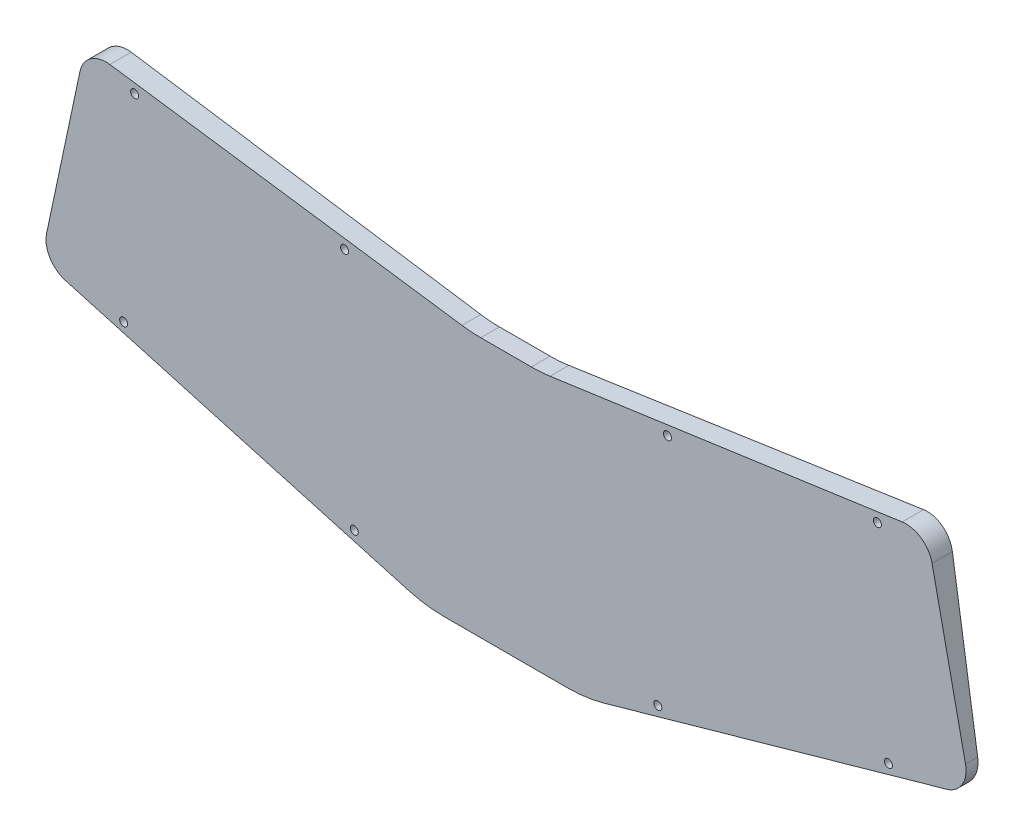
SolidWorks part; units mm, degrees
ref_plane "Front Plane" through (0, 0, 0) normal (0, 0, 1) x (1, 0, 0)
ref_plane "Top Plane" through (0, 0, 0) normal (0, 1, 0) x (1, 0, 0)
ref_plane "Right Plane" through (0, 0, 0) normal (1, 0, 0) x (0, 0, -1)
sketch "Model" plane through (0, 0, 0) normal (0, 0, 1) x (1, 0, 0)
  line L0 (325.3126, 39.9244) -> (319.5653, 66.9637)
  line L1 (325.3126, 39.9244) -> (332.0603, 8.179)
  line L2 (322.3782, 39.3007) -> (316.6308, 66.34)
  line L3 (322.3782, 39.3007) -> (329.1259, 7.5553)
  line L4 (306.4458, 71.4818) -> (308.8024, 71.8155)
  line L5 (13.8071, 71.4818) -> (11.4504, 71.8155)
  line L6 (-5.0598, 39.9244) -> (-11.8075, 8.179)
  line L7 (-2.1254, 39.3007) -> (-8.8731, 7.5553)
  line L8 (-5.0598, 39.9244) -> (0.6876, 66.9637)
  line L9 (-2.1254, 39.3007) -> (3.622, 66.34)
  line L10 (26.3327, -9.1816) -> (48.3039, -15.3856)
  line L11 (48.3039, -15.3856) -> (93.7705, -28.2242)
  line L12 (-3.9283, -0.6367) -> (7.4742, -3.8564)
  line L13 (90.0873, 60.6806) -> (30.9176, 69.0589)
  line L14 (210.7632, 57.9332) -> (177.0346, 53.1572)
  line L15 (169.604, 52.6338) -> (150.6488, 52.6338)
  line L16 (143.2182, 53.1572) -> (109.4896, 57.9332)
  line L17 (289.3352, 69.0589) -> (230.1656, 60.6806)
  line L18 (312.7787, -3.8564) -> (324.1811, -0.6367)
  line L19 (226.4824, -28.2242) -> (271.949, -15.3856)
  line L20 (271.949, -15.3856) -> (293.9202, -9.1816)
  line L21 (112.629, -33.5493) -> (124.2783, -36.8388)
  line L22 (137.0504, -38.6074) -> (160.1264, -38.6074)
  line L23 (160.1264, -38.6074) -> (183.2025, -38.6074)
  line L24 (195.9746, -36.8388) -> (207.6239, -33.5493)
  line L25 (169.604, 55.6338) -> (150.6488, 55.6338)
  line L26 (308.3818, 74.7858) -> (176.614, 56.1276)
  line L27 (272.7642, -18.2727) -> (324.9963, -3.5238)
  line L28 (196.7898, -39.7259) -> (272.7642, -18.2727)
  line L29 (160.1264, -41.6074) -> (183.2025, -41.6074)
  line L30 (137.0504, -41.6074) -> (160.1264, -41.6074)
  line L31 (47.4886, -18.2727) -> (123.463, -39.7259)
  line L32 (-4.7435, -3.5238) -> (47.4886, -18.2727)
  line L33 (143.6388, 56.1276) -> (11.8711, 74.7858)
  line L34 (196.5845, -32.4293) -> (202.5988, -29.3648)
  line L35 (190.1194, -20.2914) -> (196.2483, -32.32)
  line L36 (202.2573, -13.8263) -> (190.2287, -19.9552)
  line L37 (208.7224, -25.9641) -> (202.5935, -13.9355)
  line L38 (202.5988, -29.3648) -> (208.6131, -26.3004)
  line L39 (234.2278, -18.5408) -> (231.421, -5.3358)
  line L40 (220.8303, -21.6441) -> (234.0353, -18.8373)
  line L41 (217.7269, -8.2465) -> (220.5338, -21.4515)
  line L42 (231.1245, -5.1432) -> (217.9195, -7.95)
  line L43 (253.2284, -16.5467) -> (250.4216, -3.3417)
  line L44 (239.8309, -19.6501) -> (253.0359, -16.8433)
  line L45 (236.7276, -6.2525) -> (239.5344, -19.4575)
  line L46 (250.1251, -3.1492) -> (236.9201, -5.956)
  line L47 (210.4452, 1.9626) -> (207.6384, 15.1676)
  line L48 (197.0477, -1.1407) -> (210.2527, 1.6661)
  line L49 (193.9443, 12.2568) -> (196.7512, -0.9482)
  line L50 (207.3419, 15.3602) -> (194.1369, 12.5533)
  line L51 (206.4949, 20.5474) -> (203.6881, 33.7524)
  line L52 (193.0973, 17.4441) -> (206.3023, 20.2509)
  line L53 (189.994, 30.8416) -> (192.8008, 17.6366)
  line L54 (203.3916, 33.945) -> (190.1866, 31.1382)
  line L55 (202.5446, 39.1322) -> (199.7378, 52.3372)
  line L56 (189.147, 36.0289) -> (202.352, 38.8357)
  line L57 (186.0437, 49.4264) -> (188.8505, 36.2214)
  line L58 (199.4413, 52.5298) -> (186.2363, 49.723)
  line L59 (230.2775, 0.044) -> (227.4707, 13.249)
  line L60 (216.8799, -3.0593) -> (230.0849, -0.2525)
  line L61 (213.7766, 10.3383) -> (216.5834, -2.8667)
  line L62 (227.1742, 13.4416) -> (213.9692, 10.6348)
  line L63 (226.3272, 18.6288) -> (223.5204, 31.8338)
  line L64 (212.9296, 15.5255) -> (226.1346, 18.3323)
  line L65 (209.8263, 28.9231) -> (212.6331, 15.7181)
  line L66 (223.2239, 32.0264) -> (210.0189, 29.2196)
  line L67 (222.3769, 37.2136) -> (219.57, 50.4186)
  line L68 (208.9793, 34.1103) -> (222.1843, 36.9171)
  line L69 (205.876, 47.5079) -> (208.6828, 34.3029)
  line L70 (219.2735, 50.6112) -> (206.0685, 47.8044)
  line L71 (249.2781, 2.0381) -> (246.4713, 15.2431)
  line L72 (235.8806, -1.0653) -> (249.0856, 1.7416)
  line L73 (232.7772, 12.3323) -> (235.5841, -0.8727)
  line L74 (246.1748, 15.4356) -> (232.9698, 12.6288)
  line L75 (245.3278, 20.6229) -> (242.521, 33.8279)
  line L76 (231.9302, 17.5195) -> (245.1352, 20.3264)
  line L77 (228.8269, 30.9171) -> (231.6337, 17.7121)
  line L78 (242.2245, 34.0204) -> (229.0195, 31.2136)
  line L79 (241.3775, 39.2077) -> (238.5707, 52.4127)
  line L80 (227.9799, 36.1044) -> (241.1849, 38.9112)
  line L81 (224.8766, 49.5019) -> (227.6834, 36.2969)
  line L82 (238.2742, 52.6052) -> (225.0692, 49.7984)
  line L83 (271.2935, -10.151) -> (268.4867, 3.0539)
  line L84 (257.8959, -13.2544) -> (271.1009, -10.4476)
  line L85 (254.7926, 0.1432) -> (257.5994, -13.0618)
  line L86 (268.1901, 3.2465) -> (254.9852, 0.4397)
  line L87 (267.3431, 8.4338) -> (264.5363, 21.6387)
  line L88 (253.9456, 5.3304) -> (267.1506, 8.1372)
  line L89 (250.8423, 18.728) -> (253.6491, 5.523)
  line L90 (264.2398, 21.8313) -> (251.0348, 19.0245)
  line L91 (263.3928, 27.0186) -> (260.586, 40.2236)
  line L92 (249.9953, 23.9152) -> (263.2003, 26.722)
  line L93 (246.892, 37.3128) -> (249.6988, 24.1078)
  line L94 (260.2895, 40.4161) -> (247.0845, 37.6093)
  line L95 (259.4425, 45.6034) -> (256.6357, 58.8084)
  line L96 (246.045, 42.5) -> (259.2499, 45.3069)
  line L97 (242.9416, 55.8976) -> (245.7484, 42.6926)
  line L98 (256.3392, 59.0009) -> (243.1342, 56.1941)
  line L99 (286.4477, 9.9387) -> (283.6409, 23.1437)
  line L100 (273.0502, 6.8354) -> (286.2552, 9.6422)
  line L101 (269.9469, 20.2329) -> (272.7537, 7.0279)
  line L102 (283.3444, 23.3363) -> (270.1394, 20.5295)
  line L103 (282.4974, 28.5235) -> (279.6906, 41.7285)
  line L104 (269.0999, 25.4202) -> (282.3049, 28.227)
  line L105 (265.9965, 38.8177) -> (268.8033, 25.6128)
  line L106 (279.3941, 41.9211) -> (266.1891, 39.1143)
  line L107 (278.5471, 47.1083) -> (275.7403, 60.3133)
  line L108 (265.1495, 44.005) -> (278.3545, 46.8118)
  line L109 (262.0462, 57.4025) -> (264.853, 44.1976)
  line L110 (275.4438, 60.5059) -> (262.2388, 57.6991)
  line L111 (305.5523, 11.4437) -> (302.7455, 24.6487)
  line L112 (292.1548, 8.3403) -> (305.3598, 11.1471)
  line L113 (289.0514, 21.7379) -> (291.8582, 8.5329)
  line L114 (302.449, 24.8412) -> (289.244, 22.0344)
  line L115 (301.602, 30.0285) -> (298.7952, 43.2335)
  line L116 (288.2044, 26.9251) -> (301.4094, 29.732)
  line L117 (285.1011, 40.3227) -> (287.9079, 27.1177)
  line L118 (298.4987, 43.426) -> (285.2937, 40.6192)
  line L119 (297.6517, 48.6133) -> (294.8449, 61.8183)
  line L120 (284.2541, 45.5099) -> (297.4591, 48.3168)
  line L121 (281.1508, 58.9075) -> (283.9576, 45.7025)
  line L122 (294.5483, 62.0108) -> (281.3434, 59.204)
  line L123 (324.5529, 13.4377) -> (321.7461, 26.6427)
  line L124 (311.1554, 10.3344) -> (324.3604, 13.1412)
  line L125 (308.0521, 23.7319) -> (310.8589, 10.5269)
  line L126 (321.4496, 26.8352) -> (308.2446, 24.0284)
  line L127 (320.6026, 32.0225) -> (317.7958, 45.2275)
  line L128 (307.2051, 28.9192) -> (320.4101, 31.726)
  line L129 (304.1017, 42.3167) -> (306.9086, 29.1117)
  line L130 (317.4993, 45.42) -> (304.2943, 42.6132)
  line L131 (316.6523, 50.6073) -> (313.8455, 63.8123)
  line L132 (313.549, 64.0049) -> (300.344, 61.198)
  line L133 (300.1514, 60.9015) -> (302.9582, 47.6965)
  line L134 (303.2547, 47.504) -> (316.4597, 50.3108)
  line L135 (123.6683, -32.4293) -> (117.654, -29.3648)
  line L136 (130.1334, -20.2914) -> (124.0045, -32.32)
  line L137 (117.9956, -13.8263) -> (130.0242, -19.9552)
  line L138 (111.5305, -25.9641) -> (117.6593, -13.9355)
  line L139 (117.654, -29.3648) -> (111.6397, -26.3004)
  line L140 (86.025, -18.5408) -> (88.8318, -5.3358)
  line L141 (99.4226, -21.6441) -> (86.2176, -18.8373)
  line L142 (102.5259, -8.2465) -> (99.7191, -21.4515)
  line L143 (89.1283, -5.1432) -> (102.3333, -7.95)
  line L144 (67.0244, -16.5467) -> (69.8312, -3.3417)
  line L145 (80.4219, -19.6501) -> (67.2169, -16.8433)
  line L146 (83.5253, -6.2525) -> (80.7184, -19.4575)
  line L147 (70.1277, -3.1492) -> (83.3327, -5.956)
  line L148 (109.8076, 1.9626) -> (112.6144, 15.1676)
  line L149 (123.2052, -1.1407) -> (110.0002, 1.6661)
  line L150 (126.3085, 12.2568) -> (123.5017, -0.9482)
  line L151 (112.9109, 15.3602) -> (126.1159, 12.5533)
  line L152 (113.7579, 20.5474) -> (116.5647, 33.7524)
  line L153 (127.1555, 17.4441) -> (113.9505, 20.2509)
  line L154 (130.2588, 30.8416) -> (127.452, 17.6366)
  line L155 (116.8613, 33.945) -> (130.0662, 31.1382)
  line L156 (117.7083, 39.1322) -> (120.5151, 52.3372)
  line L157 (131.1058, 36.0289) -> (117.9008, 38.8357)
  line L158 (134.2091, 49.4264) -> (131.4023, 36.2214)
  line L159 (120.8116, 52.5298) -> (134.0166, 49.723)
  line L160 (89.9753, 0.044) -> (92.7821, 13.249)
  line L161 (103.3729, -3.0593) -> (90.1679, -0.2525)
  line L162 (106.4762, 10.3383) -> (103.6694, -2.8667)
  line L163 (93.0787, 13.4416) -> (106.2836, 10.6348)
  line L164 (93.9257, 18.6288) -> (96.7325, 31.8338)
  line L165 (107.3232, 15.5255) -> (94.1182, 18.3323)
  line L166 (110.4265, 28.9231) -> (107.6197, 15.7181)
  line L167 (97.029, 32.0264) -> (110.234, 29.2196)
  line L168 (97.876, 37.2136) -> (100.6828, 50.4186)
  line L169 (111.2735, 34.1103) -> (98.0685, 36.9171)
  line L170 (114.3769, 47.5079) -> (111.57, 34.3029)
  line L171 (100.9793, 50.6112) -> (114.1843, 47.8044)
  line L172 (70.9747, 2.0381) -> (73.7815, 15.2431)
  line L173 (84.3723, -1.0653) -> (71.1673, 1.7416)
  line L174 (87.4756, 12.3323) -> (84.6688, -0.8727)
  line L175 (74.078, 15.4356) -> (87.283, 12.6288)
  line L176 (74.925, 20.6229) -> (77.7318, 33.8279)
  line L177 (88.3226, 17.5195) -> (75.1176, 20.3264)
  line L178 (91.4259, 30.9171) -> (88.6191, 17.7121)
  line L179 (78.0284, 34.0204) -> (91.2333, 31.2136)
  line L180 (78.8753, 39.2077) -> (81.6822, 52.4127)
  line L181 (92.2729, 36.1044) -> (79.0679, 38.9112)
  line L182 (95.3762, 49.5019) -> (92.5694, 36.2969)
  line L183 (81.9787, 52.6052) -> (95.1837, 49.7984)
  line L184 (48.9594, -10.151) -> (51.7662, 3.0539)
  line L185 (62.3569, -13.2544) -> (49.1519, -10.4476)
  line L186 (65.4602, 0.1432) -> (62.6534, -13.0618)
  line L187 (52.0627, 3.2465) -> (65.2677, 0.4397)
  line L188 (52.9097, 8.4338) -> (55.7165, 21.6387)
  line L189 (66.3072, 5.3304) -> (53.1022, 8.1372)
  line L190 (69.4106, 18.728) -> (66.6037, 5.523)
  line L191 (56.013, 21.8313) -> (69.218, 19.0245)
  line L192 (56.86, 27.0186) -> (59.6668, 40.2236)
  line L193 (70.2576, 23.9152) -> (57.0526, 26.722)
  line L194 (73.3609, 37.3128) -> (70.5541, 24.1078)
  line L195 (59.9633, 40.4161) -> (73.1683, 37.6093)
  line L196 (60.8103, 45.6034) -> (63.6171, 58.8084)
  line L197 (74.2079, 42.5) -> (61.0029, 45.3069)
  line L198 (77.3112, 55.8976) -> (74.5044, 42.6926)
  line L199 (63.9136, 59.0009) -> (77.1186, 56.1941)
  line L200 (33.8051, 9.9387) -> (36.6119, 23.1437)
  line L201 (47.2026, 6.8354) -> (33.9977, 9.6422)
  line L202 (50.306, 20.2329) -> (47.4992, 7.0279)
  line L203 (36.9084, 23.3363) -> (50.1134, 20.5295)
  line L204 (37.7554, 28.5235) -> (40.5622, 41.7285)
  line L205 (51.153, 25.4202) -> (37.948, 28.227)
  line L206 (54.2563, 38.8177) -> (51.4495, 25.6128)
  line L207 (40.8587, 41.9211) -> (54.0637, 39.1143)
  line L208 (41.7057, 47.1083) -> (44.5125, 60.3133)
  line L209 (55.1033, 44.005) -> (41.8983, 46.8118)
  line L210 (58.2066, 57.4025) -> (55.3998, 44.1976)
  line L211 (44.8091, 60.5059) -> (58.0141, 57.6991)
  line L212 (14.7005, 11.4437) -> (17.5073, 24.6487)
  line L213 (28.0981, 8.3403) -> (14.8931, 11.1471)
  line L214 (31.2014, 21.7379) -> (28.3946, 8.5329)
  line L215 (17.8038, 24.8412) -> (31.0088, 22.0344)
  line L216 (18.6508, 30.0285) -> (21.4576, 43.2335)
  line L217 (32.0484, 26.9251) -> (18.8434, 29.732)
  line L218 (35.1517, 40.3227) -> (32.3449, 27.1177)
  line L219 (21.7542, 43.426) -> (34.9592, 40.6192)
  line L220 (22.6012, 48.6133) -> (25.408, 61.8183)
  line L221 (35.9987, 45.5099) -> (22.7937, 48.3168)
  line L222 (39.102, 58.9075) -> (36.2952, 45.7025)
  line L223 (25.7045, 62.0108) -> (38.9095, 59.204)
  line L224 (-4.3001, 13.4377) -> (-1.4933, 26.6427)
  line L225 (9.0974, 10.3344) -> (-4.1076, 13.1412)
  line L226 (12.2008, 23.7319) -> (9.394, 10.5269)
  line L227 (-1.1968, 26.8352) -> (12.0082, 24.0284)
  line L228 (-0.3498, 32.0225) -> (2.457, 45.2275)
  line L229 (13.0478, 28.9192) -> (-0.1572, 31.726)
  line L230 (16.1511, 42.3167) -> (13.3443, 29.1117)
  line L231 (2.7535, 45.42) -> (15.9585, 42.6132)
  line L232 (3.6005, 50.6073) -> (6.4073, 63.8123)
  line L233 (6.7039, 64.0049) -> (19.9088, 61.198)
  line L234 (20.1014, 60.9015) -> (17.2946, 47.6965)
  line L235 (16.9981, 47.504) -> (3.7931, 50.3108)
  circle A0 centre (21.1464, 69.9376) radius 1.5
  circle A1 centre (299.1065, 69.9376) radius 1.5
  arc A2 (296.6652, 67.2112) -> (289.3352, 69.0589) centre (290.7372, 59.1577) ccw
  arc A3 (306.4458, 71.4818) -> (302.641, 68.6986) centre (307.1468, 66.5312) ccw
  arc A4 (17.6118, 68.6986) -> (13.8071, 71.4818) centre (13.106, 66.5312) ccw
  arc A5 (30.9176, 69.0589) -> (23.5876, 67.2112) centre (29.5156, 59.1577) ccw
  arc A6 (17.6118, 68.6986) -> (23.5876, 67.2112) centre (21.2165, 70.4326) ccw
  arc A7 (296.6652, 67.2112) -> (302.641, 68.6986) centre (299.0364, 70.4326) ccw
  arc A8 (324.9963, -3.5238) -> (332.0603, 8.179) centre (322.2789, 6.0999) ccw
  arc A9 (319.5653, 66.9637) -> (308.3818, 74.7858) centre (309.7838, 64.8846) ccw
  arc A10 (324.1811, -0.6367) -> (329.1259, 7.5553) centre (322.2789, 6.0999) ccw
  arc A11 (316.6308, 66.34) -> (308.8024, 71.8155) centre (309.7838, 64.8846) ccw
  arc A12 (11.8711, 74.7858) -> (0.6876, 66.9637) centre (10.469, 64.8846) ccw
  arc A13 (-11.8075, 8.179) -> (-4.7435, -3.5238) centre (-2.026, 6.0999) ccw
  arc A14 (-8.8731, 7.5553) -> (-3.9283, -0.6367) centre (-2.026, 6.0999) ccw
  arc A15 (11.4504, 71.8155) -> (3.622, 66.34) centre (10.469, 64.8846) ccw
  circle A16 centre (303.2135, -6.0378) radius 1.5
  circle A17 centre (17.0393, -6.0378) radius 1.5
  arc A18 (293.9202, -9.1816) -> (299.8789, -4.5301) centre (291.2027, 0.4421) ccw
  arc A19 (305.2671, -3.0086) -> (312.7787, -3.8564) centre (310.0612, 5.7673) ccw
  arc A20 (20.3739, -4.5301) -> (26.3327, -9.1816) centre (29.0501, 0.4421) ccw
  arc A21 (7.4742, -3.8564) -> (14.9858, -3.0086) centre (10.1916, 5.7673) ccw
  arc A22 (20.3739, -4.5301) -> (14.9858, -3.0086) centre (16.9034, -6.519) ccw
  arc A23 (305.2671, -3.0086) -> (299.8789, -4.5301) centre (303.3494, -6.519) ccw
  circle A24 centre (220.5345, 58.8118) radius 1.5
  circle A25 centre (99.7183, 58.8118) radius 1.5
  arc A26 (230.1656, 60.6806) -> (223.6367, 56.8704) centre (231.5676, 50.7793) ccw
  arc A27 (218.0932, 56.0855) -> (210.7632, 57.9332) centre (212.1652, 48.032) ccw
  arc A28 (96.6161, 56.8704) -> (90.0873, 60.6806) centre (88.6852, 50.7793) ccw
  arc A29 (109.4896, 57.9332) -> (102.1596, 56.0855) centre (108.0876, 48.032) ccw
  arc A30 (218.0932, 56.0855) -> (223.6367, 56.8704) centre (220.4644, 59.3069) ccw
  arc A31 (96.6161, 56.8704) -> (102.1596, 56.0855) centre (99.7884, 59.3069) ccw
  circle A32 centre (216.9173, -30.4056) radius 1.5
  arc A33 (218.9708, -27.3764) -> (226.4824, -28.2242) centre (223.7649, -18.6005) ccw
  arc A34 (207.6239, -33.5493) -> (213.5826, -28.8979) centre (204.9064, -23.9256) ccw
  circle A35 centre (103.3356, -30.4056) radius 1.5
  arc A36 (106.6702, -28.8979) -> (112.629, -33.5493) centre (115.3464, -23.9256) ccw
  arc A37 (93.7705, -28.2242) -> (101.2821, -27.3764) centre (96.4879, -18.6005) ccw
  arc A38 (218.9708, -27.3764) -> (213.5826, -28.8979) centre (217.0531, -30.8868) ccw
  arc A39 (106.6702, -28.8979) -> (101.2821, -27.3764) centre (103.1997, -30.8868) ccw
  arc A40 (169.604, 55.6338) -> (176.614, 56.1276) centre (169.604, 105.6338) ccw
  arc A41 (183.2025, -41.6074) -> (196.7898, -39.7259) centre (183.2025, 8.3926) ccw
  arc A42 (123.463, -39.7259) -> (137.0504, -41.6074) centre (137.0504, 8.3926) ccw
  arc A43 (143.6388, 56.1276) -> (150.6488, 55.6338) centre (150.6488, 105.6338) ccw
  arc A44 (196.2483, -32.32) -> (196.5845, -32.4293) centre (196.471, -32.2065) ccw
  arc A45 (190.2287, -19.9552) -> (190.1194, -20.2914) centre (190.3422, -20.1779) ccw
  arc A46 (202.5935, -13.9355) -> (202.2573, -13.8263) centre (202.3708, -14.049) ccw
  arc A47 (208.6131, -26.3004) -> (208.7224, -25.9641) centre (208.4996, -26.0776) ccw
  arc A48 (231.421, -5.3358) -> (231.1245, -5.1432) centre (231.1765, -5.3878) ccw
  arc A49 (217.9195, -7.95) -> (217.7269, -8.2465) centre (217.9715, -8.1946) ccw
  arc A50 (220.5338, -21.4515) -> (220.8303, -21.6441) centre (220.7783, -21.3996) ccw
  arc A51 (234.0353, -18.8373) -> (234.2278, -18.5408) centre (233.9833, -18.5927) ccw
  arc A52 (250.4216, -3.3417) -> (250.1251, -3.1492) centre (250.1771, -3.3937) ccw
  arc A53 (236.9201, -5.956) -> (236.7276, -6.2525) centre (236.9721, -6.2005) ccw
  arc A54 (239.5344, -19.4575) -> (239.8309, -19.6501) centre (239.7789, -19.4055) ccw
  arc A55 (253.0359, -16.8433) -> (253.2284, -16.5467) centre (252.9839, -16.5987) ccw
  arc A56 (207.6384, 15.1676) -> (207.3419, 15.3602) centre (207.3939, 15.1156) ccw
  arc A57 (194.1369, 12.5533) -> (193.9443, 12.2568) centre (194.1889, 12.3088) ccw
  arc A58 (196.7512, -0.9482) -> (197.0477, -1.1407) centre (196.9957, -0.8962) ccw
  arc A59 (210.2527, 1.6661) -> (210.4452, 1.9626) centre (210.2007, 1.9106) ccw
  arc A60 (203.6881, 33.7524) -> (203.3916, 33.945) centre (203.4436, 33.7004) ccw
  arc A61 (190.1866, 31.1382) -> (189.994, 30.8416) centre (190.2386, 30.8936) ccw
  arc A62 (192.8008, 17.6366) -> (193.0973, 17.4441) centre (193.0454, 17.6886) ccw
  arc A63 (206.3023, 20.2509) -> (206.4949, 20.5474) centre (206.2504, 20.4954) ccw
  arc A64 (199.7378, 52.3372) -> (199.4413, 52.5298) centre (199.4932, 52.2852) ccw
  arc A65 (186.2363, 49.723) -> (186.0437, 49.4264) centre (186.2882, 49.4784) ccw
  arc A66 (188.8505, 36.2214) -> (189.147, 36.0289) centre (189.095, 36.2734) ccw
  arc A67 (202.352, 38.8357) -> (202.5446, 39.1322) centre (202.3, 39.0802) ccw
  arc A68 (227.4707, 13.249) -> (227.1742, 13.4416) centre (227.2262, 13.1971) ccw
  arc A69 (213.9692, 10.6348) -> (213.7766, 10.3383) centre (214.0212, 10.3902) ccw
  arc A70 (216.5834, -2.8667) -> (216.8799, -3.0593) centre (216.828, -2.8147) ccw
  arc A71 (230.0849, -0.2525) -> (230.2775, 0.044) centre (230.033, -0.0079) ccw
  arc A72 (223.5204, 31.8338) -> (223.2239, 32.0264) centre (223.2758, 31.7819) ccw
  arc A73 (210.0189, 29.2196) -> (209.8263, 28.9231) centre (210.0708, 28.9751) ccw
  arc A74 (212.6331, 15.7181) -> (212.9296, 15.5255) centre (212.8776, 15.7701) ccw
  arc A75 (226.1346, 18.3323) -> (226.3272, 18.6288) centre (226.0826, 18.5769) ccw
  arc A76 (219.57, 50.4186) -> (219.2735, 50.6112) centre (219.3255, 50.3667) ccw
  arc A77 (206.0685, 47.8044) -> (205.876, 47.5079) centre (206.1205, 47.5599) ccw
  arc A78 (208.6828, 34.3029) -> (208.9793, 34.1103) centre (208.9273, 34.3549) ccw
  arc A79 (222.1843, 36.9171) -> (222.3769, 37.2136) centre (222.1323, 37.1617) ccw
  arc A80 (246.4713, 15.2431) -> (246.1748, 15.4356) centre (246.2268, 15.1911) ccw
  arc A81 (249.0856, 1.7416) -> (249.2781, 2.0381) centre (249.0336, 1.9861) ccw
  arc A82 (232.9698, 12.6288) -> (232.7772, 12.3323) centre (233.0218, 12.3843) ccw
  arc A83 (235.5841, -0.8727) -> (235.8806, -1.0653) centre (235.8286, -0.8207) ccw
  arc A84 (242.521, 33.8279) -> (242.2245, 34.0204) centre (242.2765, 33.7759) ccw
  arc A85 (229.0195, 31.2136) -> (228.8269, 30.9171) centre (229.0715, 30.9691) ccw
  arc A86 (231.6337, 17.7121) -> (231.9302, 17.5195) centre (231.8783, 17.7641) ccw
  arc A87 (245.1352, 20.3264) -> (245.3278, 20.6229) centre (245.0833, 20.5709) ccw
  arc A88 (238.5707, 52.4127) -> (238.2742, 52.6052) centre (238.3261, 52.3607) ccw
  arc A89 (225.0692, 49.7984) -> (224.8766, 49.5019) centre (225.1211, 49.5539) ccw
  arc A90 (227.6834, 36.2969) -> (227.9799, 36.1044) centre (227.9279, 36.3489) ccw
  arc A91 (241.1849, 38.9112) -> (241.3775, 39.2077) centre (241.1329, 39.1557) ccw
  arc A92 (268.4867, 3.0539) -> (268.1901, 3.2465) centre (268.2421, 3.002) ccw
  arc A93 (254.9852, 0.4397) -> (254.7926, 0.1432) centre (255.0371, 0.1952) ccw
  arc A94 (257.5994, -13.0618) -> (257.8959, -13.2544) centre (257.8439, -13.0098) ccw
  arc A95 (271.1009, -10.4476) -> (271.2935, -10.151) centre (271.0489, -10.203) ccw
  arc A96 (264.5363, 21.6387) -> (264.2398, 21.8313) centre (264.2918, 21.5868) ccw
  arc A97 (251.0348, 19.0245) -> (250.8423, 18.728) centre (251.0868, 18.78) ccw
  arc A98 (253.6491, 5.523) -> (253.9456, 5.3304) centre (253.8936, 5.575) ccw
  arc A99 (267.1506, 8.1372) -> (267.3431, 8.4338) centre (267.0986, 8.3818) ccw
  arc A100 (260.586, 40.2236) -> (260.2895, 40.4161) centre (260.3415, 40.1716) ccw
  arc A101 (247.0845, 37.6093) -> (246.892, 37.3128) centre (247.1365, 37.3648) ccw
  arc A102 (249.6988, 24.1078) -> (249.9953, 23.9152) centre (249.9433, 24.1598) ccw
  arc A103 (263.2003, 26.722) -> (263.3928, 27.0186) centre (263.1483, 26.9666) ccw
  arc A104 (256.6357, 58.8084) -> (256.3392, 59.0009) centre (256.3912, 58.7564) ccw
  arc A105 (243.1342, 56.1941) -> (242.9416, 55.8976) centre (243.1862, 55.9496) ccw
  arc A106 (245.7484, 42.6926) -> (246.045, 42.5) centre (245.993, 42.7446) ccw
  arc A107 (259.2499, 45.3069) -> (259.4425, 45.6034) centre (259.198, 45.5514) ccw
  arc A108 (283.6409, 23.1437) -> (283.3444, 23.3363) centre (283.3964, 23.0917) ccw
  arc A109 (270.1394, 20.5295) -> (269.9469, 20.2329) centre (270.1914, 20.2849) ccw
  arc A110 (272.7537, 7.0279) -> (273.0502, 6.8354) centre (272.9982, 7.0799) ccw
  arc A111 (286.2552, 9.6422) -> (286.4477, 9.9387) centre (286.2032, 9.8867) ccw
  arc A112 (279.6906, 41.7285) -> (279.3941, 41.9211) centre (279.4461, 41.6765) ccw
  arc A113 (266.1891, 39.1143) -> (265.9965, 38.8177) centre (266.2411, 38.8697) ccw
  arc A114 (268.8033, 25.6128) -> (269.0999, 25.4202) centre (269.0479, 25.6647) ccw
  arc A115 (282.3049, 28.227) -> (282.4974, 28.5235) centre (282.2529, 28.4715) ccw
  arc A116 (275.7403, 60.3133) -> (275.4438, 60.5059) centre (275.4957, 60.2613) ccw
  arc A117 (262.2388, 57.6991) -> (262.0462, 57.4025) centre (262.2908, 57.4545) ccw
  arc A118 (264.853, 44.1976) -> (265.1495, 44.005) centre (265.0976, 44.2495) ccw
  arc A119 (278.3545, 46.8118) -> (278.5471, 47.1083) centre (278.3026, 47.0563) ccw
  arc A120 (302.7455, 24.6487) -> (302.449, 24.8412) centre (302.501, 24.5967) ccw
  arc A121 (305.3598, 11.1471) -> (305.5523, 11.4437) centre (305.3078, 11.3917) ccw
  arc A122 (289.244, 22.0344) -> (289.0514, 21.7379) centre (289.296, 21.7899) ccw
  arc A123 (291.8582, 8.5329) -> (292.1548, 8.3403) centre (292.1028, 8.5849) ccw
  arc A124 (298.7952, 43.2335) -> (298.4987, 43.426) centre (298.5506, 43.1815) ccw
  arc A125 (285.2937, 40.6192) -> (285.1011, 40.3227) centre (285.3457, 40.3747) ccw
  arc A126 (287.9079, 27.1177) -> (288.2044, 26.9251) centre (288.1525, 27.1697) ccw
  arc A127 (301.4094, 29.732) -> (301.602, 30.0285) centre (301.3575, 29.9765) ccw
  arc A128 (294.8449, 61.8183) -> (294.5483, 62.0108) centre (294.6003, 61.7663) ccw
  arc A129 (281.3434, 59.204) -> (281.1508, 58.9075) centre (281.3953, 58.9595) ccw
  arc A130 (283.9576, 45.7025) -> (284.2541, 45.5099) centre (284.2021, 45.7545) ccw
  arc A131 (297.4591, 48.3168) -> (297.6517, 48.6133) centre (297.4071, 48.5613) ccw
  arc A132 (321.7461, 26.6427) -> (321.4496, 26.8352) centre (321.5016, 26.5907) ccw
  arc A133 (308.2446, 24.0284) -> (308.0521, 23.7319) centre (308.2966, 23.7839) ccw
  arc A134 (310.8589, 10.5269) -> (311.1554, 10.3344) centre (311.1034, 10.5789) ccw
  arc A135 (324.3604, 13.1412) -> (324.5529, 13.4377) centre (324.3084, 13.3857) ccw
  arc A136 (317.7958, 45.2275) -> (317.4993, 45.42) centre (317.5513, 45.1755) ccw
  arc A137 (306.9086, 29.1117) -> (307.2051, 28.9192) centre (307.1531, 29.1637) ccw
  arc A138 (320.4101, 31.726) -> (320.6026, 32.0225) centre (320.3581, 31.9705) ccw
  arc A139 (304.2943, 42.6132) -> (304.1017, 42.3167) centre (304.3463, 42.3687) ccw
  arc A140 (313.8455, 63.8123) -> (313.549, 64.0049) centre (313.601, 63.7603) ccw
  arc A141 (300.344, 61.198) -> (300.1514, 60.9015) centre (300.396, 60.9535) ccw
  arc A142 (316.4597, 50.3108) -> (316.6523, 50.6073) centre (316.4078, 50.5553) ccw
  arc A143 (302.9582, 47.6965) -> (303.2547, 47.504) centre (303.2028, 47.7485) ccw
  arc A144 (123.6683, -32.4293) -> (124.0045, -32.32) centre (123.7818, -32.2065) ccw
  arc A145 (130.1334, -20.2914) -> (130.0242, -19.9552) centre (129.9107, -20.1779) ccw
  arc A146 (117.9956, -13.8263) -> (117.6593, -13.9355) centre (117.8821, -14.049) ccw
  arc A147 (111.5305, -25.9641) -> (111.6397, -26.3004) centre (111.7532, -26.0776) ccw
  arc A148 (89.1283, -5.1432) -> (88.8318, -5.3358) centre (89.0764, -5.3878) ccw
  arc A149 (102.5259, -8.2465) -> (102.3333, -7.95) centre (102.2813, -8.1946) ccw
  arc A150 (99.4226, -21.6441) -> (99.7191, -21.4515) centre (99.4745, -21.3996) ccw
  arc A151 (86.025, -18.5408) -> (86.2176, -18.8373) centre (86.2695, -18.5927) ccw
  arc A152 (70.1277, -3.1492) -> (69.8312, -3.3417) centre (70.0757, -3.3937) ccw
  arc A153 (83.5253, -6.2525) -> (83.3327, -5.956) centre (83.2807, -6.2005) ccw
  arc A154 (80.4219, -19.6501) -> (80.7184, -19.4575) centre (80.4739, -19.4055) ccw
  arc A155 (67.0244, -16.5467) -> (67.2169, -16.8433) centre (67.2689, -16.5987) ccw
  arc A156 (112.9109, 15.3602) -> (112.6144, 15.1676) centre (112.859, 15.1156) ccw
  arc A157 (126.3085, 12.2568) -> (126.1159, 12.5533) centre (126.0639, 12.3088) ccw
  arc A158 (123.2052, -1.1407) -> (123.5017, -0.9482) centre (123.2571, -0.8962) ccw
  arc A159 (109.8076, 1.9626) -> (110.0002, 1.6661) centre (110.0521, 1.9106) ccw
  arc A160 (116.8613, 33.945) -> (116.5647, 33.7524) centre (116.8093, 33.7004) ccw
  arc A161 (130.2588, 30.8416) -> (130.0662, 31.1382) centre (130.0143, 30.8936) ccw
  arc A162 (127.1555, 17.4441) -> (127.452, 17.6366) centre (127.2075, 17.6886) ccw
  arc A163 (113.7579, 20.5474) -> (113.9505, 20.2509) centre (114.0025, 20.4954) ccw
  arc A164 (120.8116, 52.5298) -> (120.5151, 52.3372) centre (120.7596, 52.2852) ccw
  arc A165 (134.2091, 49.4264) -> (134.0166, 49.723) centre (133.9646, 49.4784) ccw
  arc A166 (131.1058, 36.0289) -> (131.4023, 36.2214) centre (131.1578, 36.2734) ccw
  arc A167 (117.7083, 39.1322) -> (117.9008, 38.8357) centre (117.9528, 39.0802) ccw
  arc A168 (93.0787, 13.4416) -> (92.7821, 13.249) centre (93.0267, 13.1971) ccw
  arc A169 (106.4762, 10.3383) -> (106.2836, 10.6348) centre (106.2317, 10.3902) ccw
  arc A170 (103.3729, -3.0593) -> (103.6694, -2.8667) centre (103.4249, -2.8147) ccw
  arc A171 (89.9753, 0.044) -> (90.1679, -0.2525) centre (90.2199, -0.0079) ccw
  arc A172 (97.029, 32.0264) -> (96.7325, 31.8338) centre (96.977, 31.7819) ccw
  arc A173 (110.4265, 28.9231) -> (110.234, 29.2196) centre (110.182, 28.9751) ccw
  arc A174 (107.3232, 15.5255) -> (107.6197, 15.7181) centre (107.3752, 15.7701) ccw
  arc A175 (93.9257, 18.6288) -> (94.1182, 18.3323) centre (94.1702, 18.5769) ccw
  arc A176 (100.9793, 50.6112) -> (100.6828, 50.4186) centre (100.9273, 50.3667) ccw
  arc A177 (114.3769, 47.5079) -> (114.1843, 47.8044) centre (114.1323, 47.5599) ccw
  arc A178 (111.2735, 34.1103) -> (111.57, 34.3029) centre (111.3255, 34.3549) ccw
  arc A179 (97.876, 37.2136) -> (98.0685, 36.9171) centre (98.1205, 37.1617) ccw
  arc A180 (74.078, 15.4356) -> (73.7815, 15.2431) centre (74.026, 15.1911) ccw
  arc A181 (70.9747, 2.0381) -> (71.1673, 1.7416) centre (71.2192, 1.9861) ccw
  arc A182 (87.4756, 12.3323) -> (87.283, 12.6288) centre (87.231, 12.3843) ccw
  arc A183 (84.3723, -1.0653) -> (84.6688, -0.8727) centre (84.4242, -0.8207) ccw
  arc A184 (78.0284, 34.0204) -> (77.7318, 33.8279) centre (77.9764, 33.7759) ccw
  arc A185 (91.4259, 30.9171) -> (91.2333, 31.2136) centre (91.1814, 30.9691) ccw
  arc A186 (88.3226, 17.5195) -> (88.6191, 17.7121) centre (88.3746, 17.7641) ccw
  arc A187 (74.925, 20.6229) -> (75.1176, 20.3264) centre (75.1696, 20.5709) ccw
  arc A188 (81.9787, 52.6052) -> (81.6822, 52.4127) centre (81.9267, 52.3607) ccw
  arc A189 (95.3762, 49.5019) -> (95.1837, 49.7984) centre (95.1317, 49.5539) ccw
  arc A190 (92.2729, 36.1044) -> (92.5694, 36.2969) centre (92.3249, 36.3489) ccw
  arc A191 (78.8753, 39.2077) -> (79.0679, 38.9112) centre (79.1199, 39.1557) ccw
  arc A192 (52.0627, 3.2465) -> (51.7662, 3.0539) centre (52.0107, 3.002) ccw
  arc A193 (65.4602, 0.1432) -> (65.2677, 0.4397) centre (65.2157, 0.1952) ccw
  arc A194 (62.3569, -13.2544) -> (62.6534, -13.0618) centre (62.4089, -13.0098) ccw
  arc A195 (48.9594, -10.151) -> (49.1519, -10.4476) centre (49.2039, -10.203) ccw
  arc A196 (56.013, 21.8313) -> (55.7165, 21.6387) centre (55.961, 21.5868) ccw
  arc A197 (69.4106, 18.728) -> (69.218, 19.0245) centre (69.166, 18.78) ccw
  arc A198 (66.3072, 5.3304) -> (66.6037, 5.523) centre (66.3592, 5.575) ccw
  arc A199 (52.9097, 8.4338) -> (53.1022, 8.1372) centre (53.1542, 8.3818) ccw
  arc A200 (59.9633, 40.4161) -> (59.6668, 40.2236) centre (59.9113, 40.1716) ccw
  arc A201 (73.3609, 37.3128) -> (73.1683, 37.6093) centre (73.1163, 37.3648) ccw
  arc A202 (70.2576, 23.9152) -> (70.5541, 24.1078) centre (70.3095, 24.1598) ccw
  arc A203 (56.86, 27.0186) -> (57.0526, 26.722) centre (57.1045, 26.9666) ccw
  arc A204 (63.9136, 59.0009) -> (63.6171, 58.8084) centre (63.8617, 58.7564) ccw
  arc A205 (77.3112, 55.8976) -> (77.1186, 56.1941) centre (77.0667, 55.9496) ccw
  arc A206 (74.2079, 42.5) -> (74.5044, 42.6926) centre (74.2599, 42.7446) ccw
  arc A207 (60.8103, 45.6034) -> (61.0029, 45.3069) centre (61.0549, 45.5514) ccw
  arc A208 (36.9084, 23.3363) -> (36.6119, 23.1437) centre (36.8564, 23.0917) ccw
  arc A209 (50.306, 20.2329) -> (50.1134, 20.5295) centre (50.0614, 20.2849) ccw
  arc A210 (47.2026, 6.8354) -> (47.4992, 7.0279) centre (47.2546, 7.0799) ccw
  arc A211 (33.8051, 9.9387) -> (33.9977, 9.6422) centre (34.0496, 9.8867) ccw
  arc A212 (40.8587, 41.9211) -> (40.5622, 41.7285) centre (40.8068, 41.6765) ccw
  arc A213 (54.2563, 38.8177) -> (54.0637, 39.1143) centre (54.0118, 38.8697) ccw
  arc A214 (51.153, 25.4202) -> (51.4495, 25.6128) centre (51.2049, 25.6647) ccw
  arc A215 (37.7554, 28.5235) -> (37.948, 28.227) centre (38, 28.4715) ccw
  arc A216 (44.8091, 60.5059) -> (44.5125, 60.3133) centre (44.7571, 60.2613) ccw
  arc A217 (58.2066, 57.4025) -> (58.0141, 57.6991) centre (57.9621, 57.4545) ccw
  arc A218 (55.1033, 44.005) -> (55.3998, 44.1976) centre (55.1553, 44.2495) ccw
  arc A219 (41.7057, 47.1083) -> (41.8983, 46.8118) centre (41.9503, 47.0563) ccw
  arc A220 (17.8038, 24.8412) -> (17.5073, 24.6487) centre (17.7519, 24.5967) ccw
  arc A221 (14.7005, 11.4437) -> (14.8931, 11.1471) centre (14.945, 11.3917) ccw
  arc A222 (31.2014, 21.7379) -> (31.0088, 22.0344) centre (30.9569, 21.7899) ccw
  arc A223 (28.0981, 8.3403) -> (28.3946, 8.5329) centre (28.15, 8.5849) ccw
  arc A224 (21.7542, 43.426) -> (21.4576, 43.2335) centre (21.7022, 43.1815) ccw
  arc A225 (35.1517, 40.3227) -> (34.9592, 40.6192) centre (34.9072, 40.3747) ccw
  arc A226 (32.0484, 26.9251) -> (32.3449, 27.1177) centre (32.1004, 27.1697) ccw
  arc A227 (18.6508, 30.0285) -> (18.8434, 29.732) centre (18.8954, 29.9765) ccw
  arc A228 (25.7045, 62.0108) -> (25.408, 61.8183) centre (25.6525, 61.7663) ccw
  arc A229 (39.102, 58.9075) -> (38.9095, 59.204) centre (38.8575, 58.9595) ccw
  arc A230 (35.9987, 45.5099) -> (36.2952, 45.7025) centre (36.0507, 45.7545) ccw
  arc A231 (22.6012, 48.6133) -> (22.7937, 48.3168) centre (22.8457, 48.5613) ccw
  arc A232 (-1.1968, 26.8352) -> (-1.4933, 26.6427) centre (-1.2488, 26.5907) ccw
  arc A233 (12.2008, 23.7319) -> (12.0082, 24.0284) centre (11.9562, 23.7839) ccw
  arc A234 (9.0974, 10.3344) -> (9.394, 10.5269) centre (9.1494, 10.5789) ccw
  arc A235 (-4.3001, 13.4377) -> (-4.1076, 13.1412) centre (-4.0556, 13.3857) ccw
  arc A236 (2.7535, 45.42) -> (2.457, 45.2275) centre (2.7016, 45.1755) ccw
  arc A237 (13.0478, 28.9192) -> (13.3443, 29.1117) centre (13.0997, 29.1637) ccw
  arc A238 (-0.3498, 32.0225) -> (-0.1572, 31.726) centre (-0.1053, 31.9705) ccw
  arc A239 (16.1511, 42.3167) -> (15.9585, 42.6132) centre (15.9065, 42.3687) ccw
  arc A240 (6.7039, 64.0049) -> (6.4073, 63.8123) centre (6.6519, 63.7603) ccw
  arc A241 (20.1014, 60.9015) -> (19.9088, 61.198) centre (19.8569, 60.9535) ccw
  arc A242 (3.6005, 50.6073) -> (3.7931, 50.3108) centre (3.8451, 50.5553) ccw
  arc A243 (16.9981, 47.504) -> (17.2946, 47.6965) centre (17.0501, 47.7485) ccw
  arc A244 (169.604, 52.6338) -> (177.0346, 53.1572) centre (169.604, 105.6338) ccw
  arc A245 (143.2182, 53.1572) -> (150.6488, 52.6338) centre (150.6488, 105.6338) ccw
  arc A246 (124.2783, -36.8388) -> (137.0504, -38.6074) centre (137.0504, 8.3926) ccw
  arc A247 (183.2025, -38.6074) -> (195.9746, -36.8388) centre (183.2025, 8.3926) ccw
extrude "Boss-Extrude1" add sketch "Model" along normal blind 8 contours L23 A247 L24 A34 A38 A33 L19 L20 A18 A23 A19 L18 A10 L3 L2 A11 L4 A3 A7 A2 L17 A26 A30 A27 L14 A244 L15 A245 L16 A29 A31 A28 L13 A5 A6 A4 L5 A15 L9 L7 A14 L12 A21 A22 A20 L10 L11 A37 A39 A36 L21 | A43 L33 A12 L8 L6 A13 L32 L31 A42 L30 L29 A41 L28 L27 A8 L1 L0 A9 L26 A40 L25 A247 L23 L22 A246 L21 A36 A39 A37 L11 L10 A20 A22 A21 L12 A14 L7 L9 A15 L5 A4 A6 A5 L13 A28 A31 A29 L16 A245 L15 | L235 A243 L234 A241 L233 A240 L232 A242 | L220 A231 L221 A230 L222 A229 L223 A228 | L216 A227 L217 A226 L218 A225 L219 A224 | L230 A239 L231 A236 L228 A238 L229 A237 | L224 A235 L225 A234 L226 A233 L227 A232 | L213 A223 L214 A222 L215 A220 L212 A221 | L200 A211 L201 A210 L202 A209 L203 A208 | L204 A215 L205 A214 L206 A213 L207 A212 | L208 A219 L209 A218 L210 A217 L211 A216 | L196 A207 L197 A206 L198 A205 L199 A204 | L192 A203 L193 A202 L194 A201 L195 A200 | L188 A199 L189 A198 L190 A197 L191 A196 | L184 A195 L185 A194 L186 A193 L187 A192 | L144 A155 L145 A154 L146 A153 L147 A152 | L140 A151 L141 A150 L142 A149 L143 A148 | L160 A171 L161 A170 L162 A169 L163 A168 | L173 A183 L174 A182 L175 A180 L172 A181 | L176 A187 L177 A186 L178 A185 L179 A184 | L180 A191 L181 A190 L182 A189 L183 A188 | L168 A179 L169 A178 L170 A177 L171 A176 | L152 A163 L153 A162 L154 A161 L155 A160 | L148 A159 L149 A158 L150 A157 L151 A156 | L138 A147 L139 L135 A144 L136 A145 L137 A146 | L164 A175 L165 A174 L166 A173 L167 A172 | L156 A167 L157 A166 L158 A165 L159 A164 | L56 A67 L55 A64 L58 A65 L57 A66 | L52 A63 L51 A60 L54 A61 L53 A62 | L48 A59 L47 A56 L50 A57 L49 A58 | L38 A47 L37 A46 L36 A45 L35 A44 L34 | L40 A51 L39 A48 L42 A49 L41 A50 | L44 A55 L43 A52 L46 A53 L45 A54 | L84 A95 L83 A92 L86 A93 L85 A94 | L88 A99 L87 A96 L90 A97 L89 A98 | L73 A83 L72 A81 L71 A80 L74 A82 | L60 A71 L59 A68 L62 A69 L61 A70 | L64 A75 L63 A72 L66 A73 L65 A74 | L68 A79 L67 A76 L70 A77 L69 A78 | L80 A91 L79 A88 L82 A89 L81 A90 | L76 A87 L75 A84 L78 A85 L77 A86 | L92 A103 L91 A100 L94 A101 L93 A102 | L96 A107 L95 A104 L98 A105 L97 A106 | L108 A119 L107 A116 L110 A117 L109 A118 | L104 A115 L103 A112 L106 A113 L105 A114 | L100 A111 L99 A108 L102 A109 L101 A110 | L113 A123 L112 A121 L111 A120 L114 A122 | L116 A127 L115 A124 L118 A125 L117 A126 | L120 A131 L119 A128 L122 A129 L121 A130 | L133 A143 L134 A142 L131 A140 L132 A141 | L130 A139 L129 A137 L128 A138 L127 A136 | L124 A135 L123 A132 L126 A133 L125 A134 region at (328.331, 23.9762, 0) region at (160.1264, 15.5989, 0) region at (199.4209, -23.1278, 0) region at (225.9774, -13.3937, 0) region at (244.978, -11.3996, 0) region at (202.1948, 7.1097, 0) region at (198.2445, 25.6945, 0) region at (194.2941, 44.2793, 0) region at (222.0271, 5.1912, 0) region at (218.0767, 23.776, 0) region at (214.1264, 42.3608, 0) region at (241.0277, 7.1852, 0) region at (237.0774, 25.77, 0) region at (233.127, 44.3548, 0) region at (263.043, -5.0039, 0) region at (259.0927, 13.5809, 0) region at (255.1424, 32.1657, 0) region at (251.1921, 50.7505, 0) region at (278.1973, 15.0858, 0) region at (274.247, 33.6706, 0) region at (270.2967, 52.2554, 0) region at (297.3019, 16.5908, 0) region at (293.3516, 35.1756, 0) region at (289.4012, 53.7604, 0) region at (316.3025, 18.5848, 0) region at (312.3522, 37.1696, 0) region at (308.4019, 55.7544, 0) region at (120.8319, -23.1278, 0) region at (94.2754, -13.3937, 0) region at (75.2748, -11.3996, 0) region at (118.058, 7.1097, 0) region at (122.0084, 25.6945, 0) region at (125.9587, 44.2793, 0) region at (98.2258, 5.1912, 0) region at (102.1761, 23.776, 0) region at (106.1264, 42.3608, 0) region at (79.2251, 7.1852, 0) region at (83.1755, 25.77, 0) region at (87.1258, 44.3548, 0) region at (57.2098, -5.0039, 0) region at (61.1601, 13.5809, 0) region at (65.1104, 32.1657, 0) region at (69.0608, 50.7505, 0) region at (42.0555, 15.0858, 0) region at (46.0059, 33.6706, 0) region at (49.9562, 52.2554, 0) region at (22.9509, 16.5908, 0) region at (26.9013, 35.1756, 0) region at (30.8516, 53.7604, 0) region at (3.9503, 18.5848, 0) region at (7.9006, 37.1696, 0) region at (11.851, 55.7544, 0)
extrude "Boss-Extrude2" add sketch "Model<3>" along normal blind 8 contours A43 L33 A12 L8 L6 A13 L32 L31 A42 L30 L29 A41 L28 L27 A8 L1 L0 A9 L26 A40 L25 A247 L23 L22 A246 L21 A36 A39 A37 L11 L10 A20 A22 A21 L12 A14 L7 L9 A15 L5 A4 A6 A5 L13 A28 A31 A29 L16 A245 L15 region at (328.331, 23.9762, 0)
sketch "Model<3>" plane through (0, 0, 0) normal (0, 0, 1) x (1, 0, 0) same geometry as "Model"
sketch "Sketch2" plane through (0, 0, 0) normal (1, 0, 0) x (0, 0, -1)
  line L3 (0, -41.6074) -> (-6, -41.6074)
  line L7 (-8, -41.6074) -> (0, -41.6074) construction
  line L8 (-6, -41.6074) -> (0, 74.8846)
  line L9 (0, 74.8846) -> (0, -41.6074)
extrude "Cut-Extrude2" cut sketch "Sketch2" against normal through all both and the other way through all contours L3 region at (0, -2.7768, 2)
